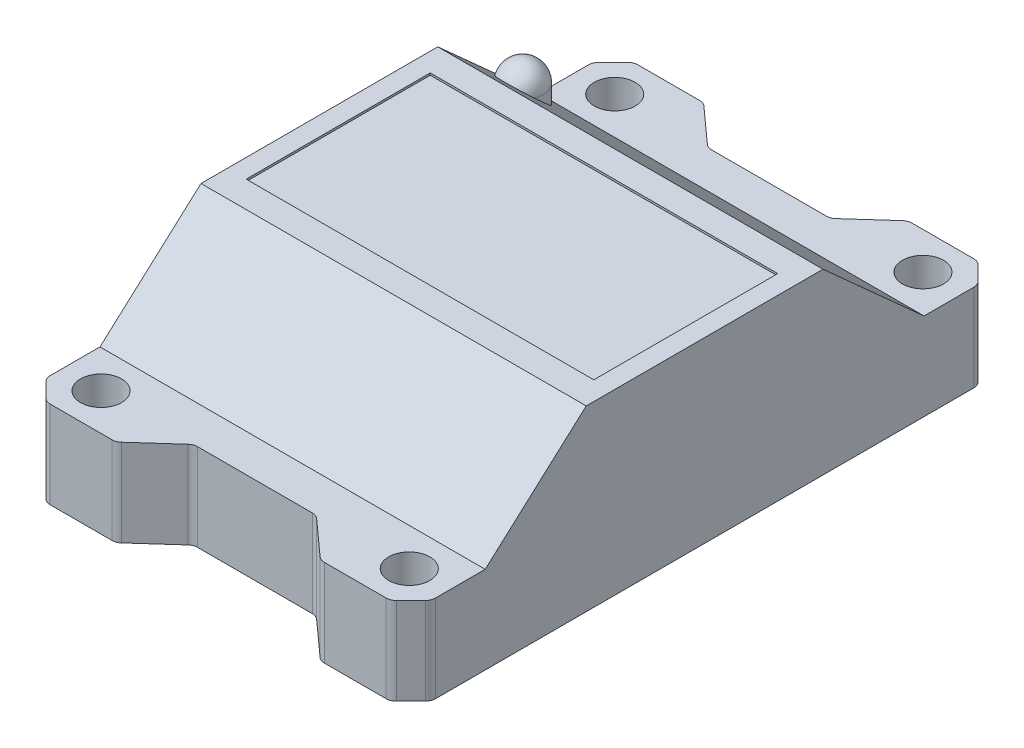
SolidWorks part; units mm, degrees
ref_plane "Front Plane" through (0, 0, 0) normal (0, 0, 1) x (1, 0, 0)
ref_plane "Top Plane" through (0, 0, 0) normal (0, 1, 0) x (1, 0, 0)
ref_plane "Right Plane" through (0, 0, 0) normal (1, 0, 0) x (0, 0, -1)
sketch "Sketch1" plane through (0, 0, 0) normal (0, 1, 0) x (1, 0, 0)
  line L1 (23.9306, -36.5036) -> (-23.9306, -36.5036)
  line L2 (23.9306, -36.5036) -> (23.9306, 36.5036)
  line L3 (23.9306, 36.5036) -> (-23.9306, 36.5036)
  line L4 (-23.9306, -36.5036) -> (-23.9306, 36.5036)
  line L5 (23.9306, -36.5036) -> (-23.9306, 36.5036) construction
  line L6 (23.9306, 36.5036) -> (-23.9306, -36.5036) construction
  line L7 (19.1452, -31.9088) -> (-19.1453, -31.9088) construction
  line L8 (19.1452, -31.9088) -> (19.1452, 31.9088) construction
  line L9 (19.1452, 31.9088) -> (-19.1453, 31.9088) construction
  line L10 (-19.1453, -31.9088) -> (-19.1453, 31.9088) construction
  line L11 (19.1452, -31.9088) -> (-19.1453, 31.9088) construction
  line L12 (19.1452, 31.9088) -> (-19.1453, -31.9088) construction
  circle A0 centre (-19.1453, 31.9088) radius 2.5527
  circle A1 centre (19.1452, 31.9088) radius 2.5527
  circle A2 centre (19.1452, -31.9088) radius 2.5527
  circle A3 centre (-19.1453, -31.9088) radius 2.5527
  point P0 (0, 0)
  point P6 (0, 0)
  dimension "D1" = 5.1054
  dimension "D2" = 38.2905
  dimension "D3" = 63.8175
  dimension "D4" = 73.0072
  dimension "D5" = 47.8612
extrude "Boss-Extrude1" add sketch "Sketch1" along normal blind 22.1412
sketch "Sketch2" plane through (0, 0, 0) normal (1, 0, 0) x (0, 0, -1)
  line L0 (0, 30.6594) -> (0, -12.3249) construction
  line L1 (14.7066, 22.1412) -> (-14.7066, 22.1412)
  line L2 (-36.5036, 22.1412) -> (36.5036, 22.1412) construction
  line L3 (-14.7066, 22.1412) -> (-27.2599, 10.8382)
  line L4 (14.7066, 22.1412) -> (27.2599, 10.8382)
  line L5 (-27.2599, 10.8382) -> (-36.5036, 10.8382)
  line L7 (-36.5036, 10.8382) -> (-45.5506, 42.0741)
  line L8 (-14.7066, 22.1412) -> (-14.7066, 10.8382) construction
  line L9 (14.7066, 22.1412) -> (14.7066, 10.8382) construction
  line L10 (-14.7066, 10.8382) -> (-27.2599, 10.8382) construction
  line L11 (14.7066, 10.8382) -> (27.2599, 10.8382) construction
  line L12 (-36.5036, 22.1412) -> (-36.5036, 0) construction
  line L13 (27.2599, 10.8382) -> (36.5036, 10.8382)
  line L14 (36.5036, 10.8382) -> (45.5506, 42.0741)
  line L15 (-45.5506, 42.0741) -> (0, 43.6302)
  line L16 (45.5506, 42.0741) -> (0, 43.6302)
  point P8 (0, 22.1412)
  dimension "D1" = 11.303
  dimension "D2" = 138
  dimension "D3" = 29.4132
extrude "Cut-Extrude1" cut sketch "Sketch2" against normal through all and the other way through all
chamfer "Chamfer1" distance 2.54 angle 45 4 edges at (-23.9306, 5.4191, -36.5036) (23.9306, 5.4191, -36.5036) (-23.9306, 5.4191, 36.5036) (23.9306, 5.4191, 36.5036)
sketch "Sketch4" plane through (0, 0, 0) normal (0, 1, 0) x (1, 0, 0)
  line L0 (-30.7199, 0) -> (35.7189, 0) construction
  line L1 (-12.7, 36.5036) -> (-7.62, 31.9316)
  line L2 (-21.3906, 36.5036) -> (21.3906, 36.5036) construction
  line L3 (-12.7, -36.5036) -> (-7.62, -31.9316)
  line L4 (-7.62, 31.9316) -> (7.62, 31.9316)
  line L5 (-7.62, -31.9316) -> (7.62, -31.9316)
  line L6 (7.62, 31.9316) -> (12.7, 36.5036)
  line L7 (7.62, -31.9316) -> (12.7, -36.5036)
  line L8 (12.7, 36.5036) -> (-12.7, 36.5036)
  line L9 (12.7, -36.5036) -> (-12.7, -36.5036)
  line L10 (0, 36.5036) -> (0, 31.9316) construction
  line L11 (0, -36.5036) -> (0, -31.9316) construction
  point P13 (0, 31.9316)
  point P14 (0, 36.5036)
  dimension "D1" = 4.572
  dimension "D2" = 25.4
  dimension "D3" = 15.24
extrude "Cut-Extrude2" cut sketch "Sketch4" along normal through all
sketch "Sketch5" plane through (0, 22.1412, 0) normal (0, 1, 0) x (1, 0, 0)
  line L1 (21.59, -11.43) -> (-21.59, -11.43)
  line L2 (21.59, -11.43) -> (21.59, 11.43)
  line L3 (21.59, 11.43) -> (-21.59, 11.43)
  line L4 (-21.59, -11.43) -> (-21.59, 11.43)
  line L5 (21.59, -11.43) -> (-21.59, 11.43) construction
  line L6 (21.59, 11.43) -> (-21.59, -11.43) construction
  point P0 (0, 0)
  dimension "D1" = 22.86
  dimension "D2" = 43.18
extrude "Cut-Extrude3" cut sketch "Sketch5" against normal blind 0.254
sketch "Sketch6" plane through (0, 0, 0) normal (0, 1, 0) x (1, 0, 0)
  line L0 (0, 0) -> (0, -5.5764) construction
  line L1 (20.32, -5.5764) -> (-20.32, -5.5764) construction
  text T0 "SPARK" font "Impact" height in points 42
  point P6 (0, -5.5764)
  dimension "D1" = 40.64
extrude "TEXT" [suppressed] add sketch "Sketch6" along normal up to surface (22.1412 mm away)
sketch "Sketch7" plane through (0, 0, 0) normal (0, 1, 0) x (1, 0, 0)
  line L0 (-19.1453, 20.4788) -> (-19.1453, 31.9088) construction
  circle A0 centre (-19.1453, 20.4788) radius 2.54
  dimension "D1" = 5.08
  dimension "D2" = 11.43
extrude "Boss-Extrude3" add sketch "Sketch7" along normal blind 20.32
fillet "Fillet1" radius 2.54 1 edges at (-19.1453, 20.32, -17.9387)
fillet "Fillet2" radius 1.27 16 edges at (23.9306, 5.4191, -33.9636) (21.3906, 5.4191, -36.5036) (12.7, 5.4191, -36.5036) (7.62, 5.4191, -31.9316) (-12.7, 5.4191, -36.5036) (-7.62, 5.4191, -31.9316) (-21.3906, 5.4191, -36.5036) (-23.9306, 5.4191, -33.9636) (-23.9306, 5.4191, 33.9636) (-21.3906, 5.4191, 36.5036) (23.9306, 5.4191, 33.9636) (21.3906, 5.4191, 36.5036) (12.7, 5.4191, 36.5036) (7.62, 5.4191, 31.9316) (-7.62, 5.4191, 31.9316) (-12.7, 5.4191, 36.5036)
